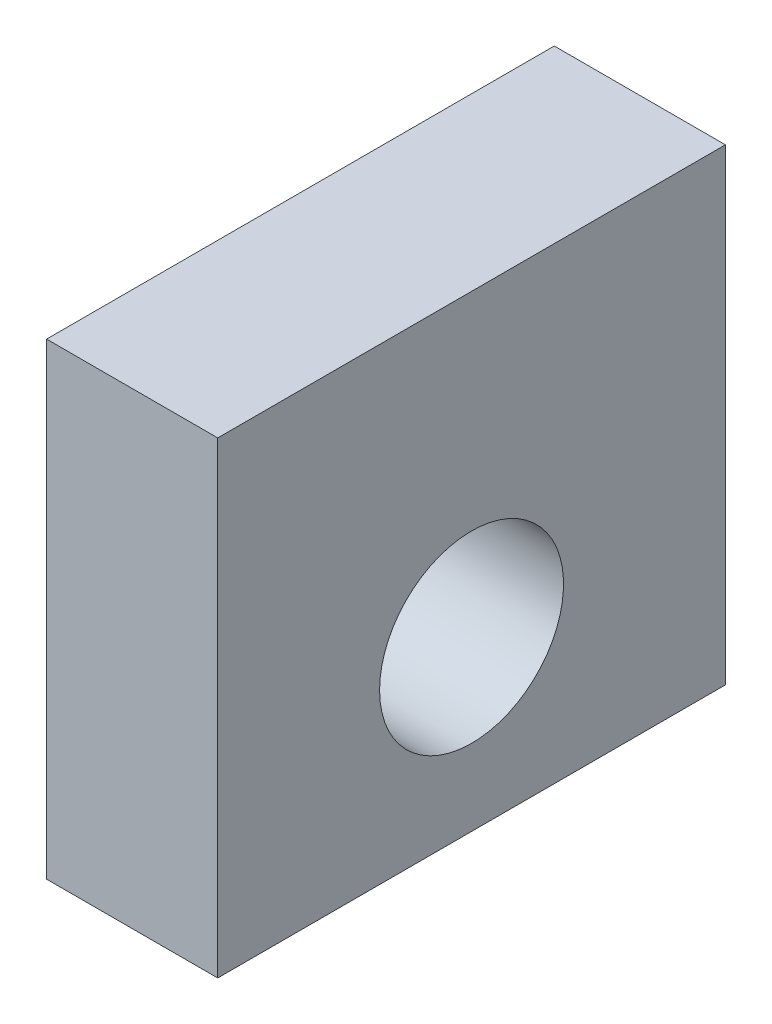
SolidWorks part; units mm, degrees
ref_plane "Front Plane" through (0, 0, 0) normal (0, 0, 1) x (1, 0, 0)
ref_plane "Top Plane" through (0, 0, 0) normal (0, 1, 0) x (1, 0, 0)
ref_plane "Right Plane" through (0, 0, 0) normal (1, 0, 0) x (0, 0, -1)
sketch "Block Sketch" plane through (0, 0, 0) normal (1, 0, 0) x (0, 0, -1)
  line L0 (8.9, 82.1) -> (-8.9, 82.1)
  line L1 (-8.9, 82.1) -> (-8.9, 98.5)
  line L2 (-8.9, 98.5) -> (8.9, 98.5)
  line L3 (8.9, 98.5) -> (8.9, 82.1)
extrude "Block" add sketch "Block Sketch" along normal mid plane 6
ref_axis "Engine Axis" through (3.3, 0, 0) along (-1, 0, 0)
sketch "Tube Hole Sketch" plane through (0, 0, 0) normal (1, 0, 0) x (0, 0, -1)
  circle A0 centre (0, 88) radius 3.225
extrude "Tube Hole" cut sketch "Tube Hole Sketch" against normal mid plane 8
